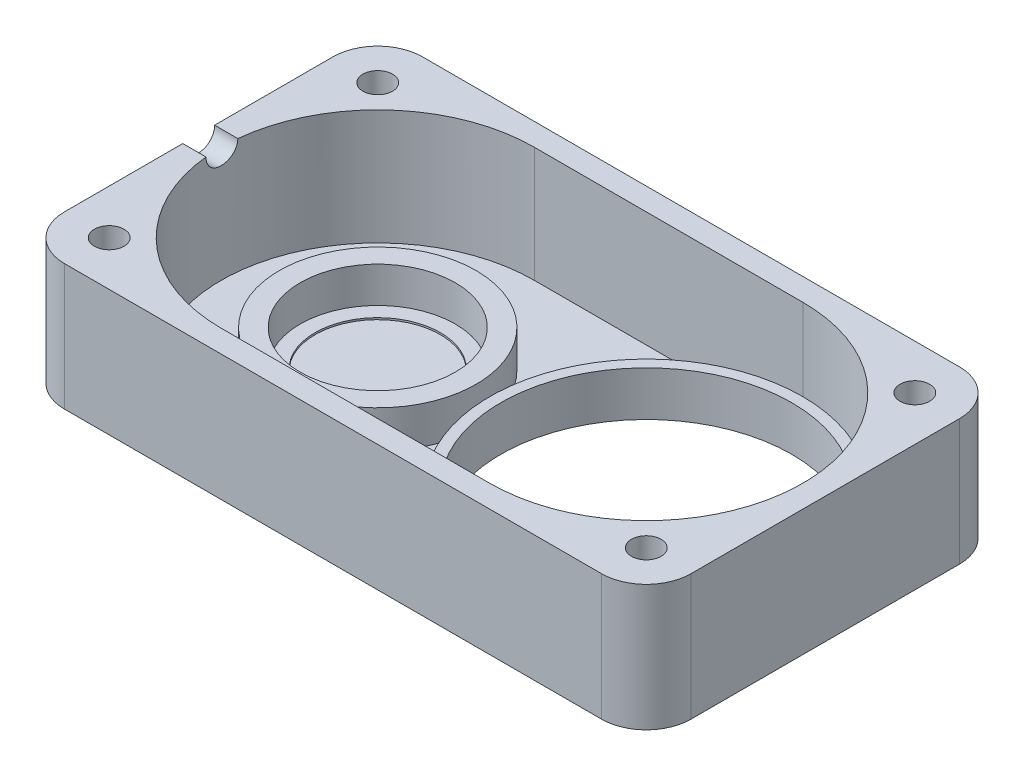
SolidWorks part; units mm, degrees
ref_plane "Front Plane" through (0, 0, 0) normal (0, 0, 1) x (1, 0, 0)
ref_plane "Top Plane" through (0, 0, 0) normal (0, 1, 0) x (1, 0, 0)
ref_plane "Right Plane" through (0, 0, 0) normal (1, 0, 0) x (0, 0, -1)
sketch "Sketch1" plane through (0, 0, 0) normal (0, 1, 0) x (1, 0, 0)
  line L0 (38.1, 19.05) -> (38.1, 25.4) construction
  line L1 (-19.05, -25.4) -> (57.15, -25.4)
  line L2 (-25.4, -19.05) -> (-25.4, 19.05)
  line L3 (-19.05, 25.4) -> (57.15, 25.4)
  line L4 (63.5, -19.05) -> (63.5, 19.05)
  line L5 (-25.4, -25.4) -> (63.5, 25.4) construction
  line L6 (-25.4, 25.4) -> (63.5, -25.4) construction
  line L7 (57.15, 0) -> (63.5, 0) construction
  line L9 (-7.62, -11.176) -> (7.62, -11.176) construction
  line L10 (-7.62, -11.176) -> (-7.62, 11.176) construction
  line L11 (-7.62, 11.176) -> (7.62, 11.176) construction
  line L12 (7.62, -11.176) -> (7.62, 11.176) construction
  line L13 (-7.62, -11.176) -> (7.62, 11.176) construction
  line L14 (-7.62, 11.176) -> (7.62, -11.176) construction
  circle A0 centre (0, 0) radius 19.05 construction
  circle A1 centre (38.1, 0) radius 19.05 construction
  circle A2 centre (38.1, 0) radius 12.7 construction
  circle A3 centre (38.1, 0) radius 20.6375
  arc A4 (-25.4, 19.05) -> (-19.05, 25.4) centre (-19.05, 19.05) cw
  arc A5 (-19.05, -25.4) -> (-25.4, -19.05) centre (-19.05, -19.05) cw
  arc A6 (57.15, -25.4) -> (63.5, -19.05) centre (57.15, -19.05) ccw
  arc A7 (57.15, 25.4) -> (63.5, 19.05) centre (57.15, 19.05) cw
  circle A8 centre (-19.05, 19.05) radius 2.1
  circle A9 centre (-19.05, -19.05) radius 2.1
  circle A10 centre (57.15, -19.05) radius 2.1
  circle A11 centre (57.15, 19.05) radius 2.1
  point P6 (19.05, 0)
  dimension "D1" = 38.1
  dimension "D2" = 38.1
  dimension "D3" = 50.8
  dimension "D7" = 25.4
  dimension "D8" = 41.275
  dimension "D9" = 6.35
  dimension "D10" = 4.2
  dimension "D4" = 88.9
  dimension "D5" = 15.24
  dimension "D6" = 22.352
extrude "Boss-Extrude1" add sketch "Sketch1" along normal blind 17.8791
sketch "Sketch2" plane through (0, 17.8791, 0) normal (0, 1, 0) x (1, 0, 0)
  line L0 (0, 22.225) -> (38.1, 22.225)
  line L1 (38.1, -22.225) -> (0, -22.225)
  arc A0 (0, 22.225) -> (0, -22.225) centre (0, 0) ccw
  arc A1 (38.1, -22.225) -> (38.1, 22.225) centre (38.1, 0) ccw
  dimension "D1" = 44.45
extrude "Cut-Extrude1" cut sketch "Sketch2" against normal offset from surface (16.3551 mm away) 1.524 up to face at (57.15, 0, 21.15)
sketch "Sketch3" plane through (0, 1.524, 0) normal (0, 1, 0) x (1, 0, 0)
  circle A0 centre (0, 0) radius 13.97
  circle A1 centre (0, 0) radius 8.89
  dimension "D1" = 27.94
  dimension "D2" = 17.78
extrude "Boss-Extrude2" add sketch "Sketch3" along normal blind 0.254
sketch "Sketch4" plane through (0, 1.778, 0) normal (0, 1, 0) x (1, 0, 0)
  circle A0 centre (0, 0) radius 10.9995
  circle A1 centre (0, 0) radius 13.97 construction
  circle A2 centre (0, 0) radius 13.97
  dimension "D1" = 21.9989
extrude "Boss-Extrude3" add sketch "Sketch4" along normal blind 5.08
sketch "Sketch5" plane through (0, 1.524, 0) normal (0, 1, 0) x (1, 0, 0)
  circle A0 centre (38.1, 0) radius 22.1615
  circle A1 centre (38.1, 0) radius 20.6375 construction
  circle A2 centre (38.1, 0) radius 20.6375
  dimension "D1" = 1.524
extrude "Boss-Extrude4" add sketch "Sketch5" along normal blind 4.826
sketch "Sketch6" plane through (-25.4, 0, 0) normal (-1, 0, 0) x (0, 0, 1)
  line L0 (-19.05, 17.8791) -> (19.05, 17.8791) construction
  circle A0 centre (0, 17.8791) radius 2.2606
  dimension "D1" = 4.5212
extrude "Cut-Extrude2" cut sketch "Sketch6" against normal up to next
sketch "Sketch7" plane through (0, 0, 0) normal (0, -1, 0) x (1, 0, 0)
  circle A0 centre (-19.05, 19.05) radius 3.75
  circle A1 centre (-19.05, -19.05) radius 3.75
  circle A2 centre (57.15, -19.05) radius 3.75
  circle A3 centre (57.15, 19.05) radius 3.75
  dimension "D1" = 7.5
extrude "Cut-Extrude3" cut sketch "Sketch7" against normal blind 4.5
